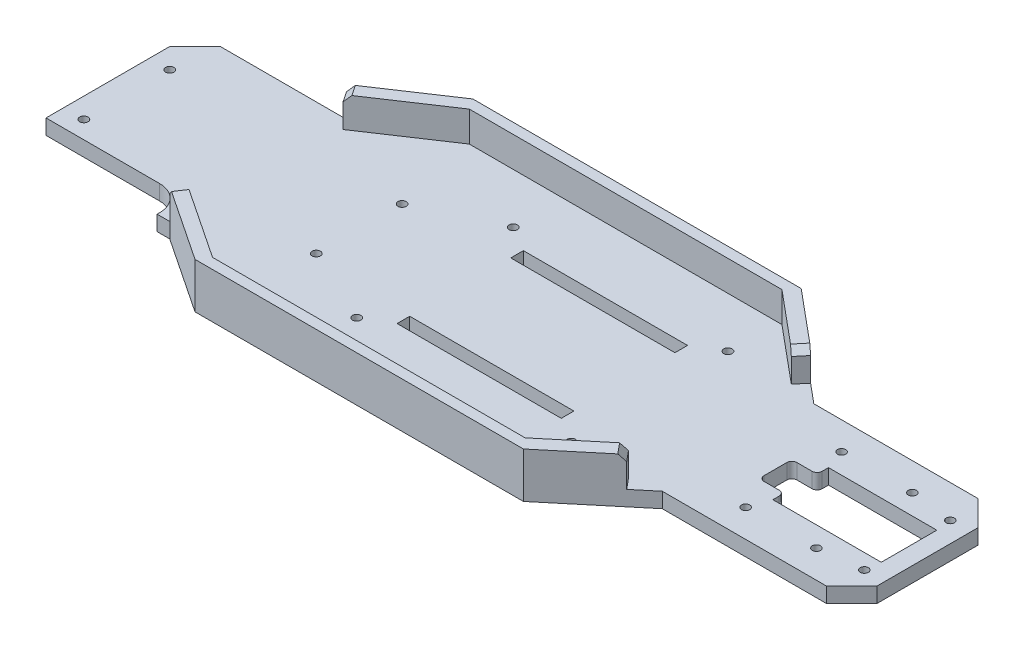
SolidWorks part; units mm, degrees
material "PETG - Polymaker"
ref_plane "Front Plane" through (0, 0, 0) normal (0, 0, 1) x (1, 0, 0)
ref_plane "Top Plane" through (0, 0, 0) normal (0, 1, 0) x (1, 0, 0)
ref_plane "Right Plane" through (0, 0, 0) normal (1, 0, 0) x (0, 0, -1)
sketch "Sketch1" plane through (0, 0, 0) normal (0, 1, 0) x (1, 0, 0)
  line L0 (-235.1499, 0) -> (235.1499, 0) construction
  line L1 (0, 0) -> (0, 52596.8311) construction
  line L2 (-95, 35) -> (-65, 55)
  line L3 (-65, 55) -> (65, 55)
  line L4 (-95, 35) -> (-155, 35)
  line L5 (-155, 35) -> (-155, -35)
  line L6 (-65, -55) -> (65, -55)
  line L7 (-95, -35) -> (-65, -55)
  line L8 (-95, -35) -> (-155, -35)
  line L9 (65, 55) -> (95, 30)
  line L10 (95, 30) -> (170, 30)
  line L11 (170, 30) -> (170, -30)
  line L12 (95, -30) -> (170, -30)
  line L13 (65, -55) -> (95, -30)
  point P3 (0, 0)
  point P10 (-80, 45)
  point P15 (-80, -45)
  point P18 (-155, 0)
  point P19 (0, -55)
  point P20 (0, 55)
  point P23 (170, 0)
  dimension "D1" = 55
  dimension "D2" = 70
  dimension "D3" = 30
  dimension "D4" = 60
  dimension "D5" = 130
  dimension "D6" = 75
  dimension "D7" = 60
  dimension "D8" = 30
  dimension "D9" = 110
extrude "Boss-Extrude1" add sketch "Sketch1" along normal blind 6
sketch "Sketch3" plane through (0, 6, 0) normal (0, 1, 0) x (1, 0, 0)
  line L0 (0, 0) -> (50000, 0) construction
  line L1 (0, 0) -> (0, 50000) construction
  line L2 (0, 55) -> (-65, 55)
  line L3 (65, 55) -> (-65, 55) construction
  line L4 (-65, 55) -> (-95, 35)
  line L5 (-95, 35) -> (-92.2265, 30.8397)
  line L6 (-92.2265, 30.8397) -> (-62.2265, 50.8397)
  line L7 (-62.2265, 50.8397) -> (0, 50.8397)
  line L8 (-65, 55) -> (-62.2265, 50.8397) construction
  line L9 (0, 55) -> (65, 55)
  line L10 (65, 55) -> (87.3178, 36.4018)
  line L11 (87.3178, 36.4018) -> (83.8509, 32.2416)
  line L12 (83.8509, 32.2416) -> (61.5331, 50.8397)
  line L13 (61.5331, 50.8397) -> (0, 50.8397)
  line L14 (61.5331, 50.8397) -> (65, 55) construction
  line L15 (61.5331, -50.8397) -> (65, -55) construction
  line L16 (-65, -55) -> (-62.2265, -50.8397) construction
  line L27 (-65, 55) -> (-95, 35) construction
  line L28 (95, 30) -> (65, 55) construction
  line L29 (61.5331, -50.8397) -> (0, -50.8397)
  line L30 (83.8509, -32.2416) -> (61.5331, -50.8397)
  line L31 (87.3178, -36.4018) -> (83.8509, -32.2416)
  line L32 (65, -55) -> (87.3178, -36.4018)
  line L33 (0, -55) -> (65, -55)
  line L34 (-62.2265, -50.8397) -> (0, -50.8397)
  line L35 (-92.2265, -30.8397) -> (-62.2265, -50.8397)
  line L36 (-95, -35) -> (-92.2265, -30.8397)
  line L37 (-65, -55) -> (-95, -35)
  line L38 (0, -55) -> (-65, -55)
  dimension "D1" = 5
  dimension "D2" = 0
  dimension "D3" = 10
extrude "Chassis-Walls1" add sketch "Sketch3" along normal blind 12
chamfer "Chamfer1" distance 10 angle 45 2 edges at (-155, 3, -35) (-155, 3, 35)
chamfer "Chamfer2" distance 10 angle 45 2 edges at (170, 3, -30) (170, 3, 30)
chamfer "Chamfer3" distance 2.5 angle 45 4 edges at (-93.6132, 18, -32.9199) (85.5843, 18, -34.3217) (-93.6132, 18, 32.9199) (85.5843, 18, 34.3217)
sketch "Sketch4" plane through (0, 0, 0) normal (0, -1, 0) x (1, 0, 0)
  line L0 (0, 0) -> (50000, 0) construction
  line L1 (-147, 17) -> (-55, 17) construction
  line L2 (-155, -25) -> (-155, 25) construction
  circle A0 centre (-147, 17) radius 1.65
  circle A1 centre (-55, 17) radius 1.65
  circle A2 centre (-55, -17) radius 1.65
  circle A3 centre (-147, -17) radius 1.65
  circle A4 centre (-25, 31) radius 1.65
  circle A5 centre (60, 31) radius 1.65
  circle A6 centre (60, -31) radius 1.65
  circle A7 centre (-25, -31) radius 1.65
  dimension "D1" = 3.3
  dimension "D2" = 3.3
  dimension "D6" = 3.3
  dimension "D8" = 3.3
  dimension "D3" = 8
  dimension "D4" = 92
  dimension "D5" = 34
  dimension "D7" = 30
  dimension "D9" = 85
  dimension "D10" = 62
extrude "Cut-Extrude1" cut sketch "Sketch4" against normal blind 10
sketch "Sketch5" plane through (0, 6, 0) normal (0, 1, 0) x (1, 0, 0)
  line L0 (-155, -24) -> (-100, -24)
  line L1 (-155, 25) -> (-155, -25) construction
  line L2 (-100, -24) -> (-100, -35)
  line L3 (-145, -35) -> (-95, -35) construction
  line L4 (-100, -35) -> (-155, -35)
  line L5 (-155, -35) -> (-155, -24)
  dimension "D1" = 55
  dimension "D2" = 11
extrude "Cut-Extrude2" cut sketch "Sketch5" against normal blind 10
sketch "Sketch6" plane through (0, 6, 0) normal (0, 1, 0) x (1, 0, 0)
  line L0 (0, 0) -> (50000, 0) construction
  line L1 (60, 31) -> (-25, 31) construction
  line L2 (17.5, 30.75) -> (17.5, 50030.75) construction
  line L3 (-15, -20) -> (50, -25) construction
  line L4 (-15, 25) -> (50, 25)
  line L5 (-15, 25) -> (-15, 20)
  line L6 (-15, 20) -> (50, 20)
  line L7 (50, 25) -> (50, 20)
  line L8 (-15, 25) -> (50, 20) construction
  line L9 (-15, 20) -> (50, 25) construction
  line L10 (-15, -25) -> (50, -20) construction
  line L11 (50, -25) -> (50, -20)
  line L12 (-15, -20) -> (50, -20)
  line L13 (-15, -25) -> (-15, -20)
  line L14 (-15, -25) -> (50, -25)
  point P9 (17.5, 31)
  point P10 (17.5, 22.5)
  point P19 (17.5, -22.5)
  dimension "D1" = 5
  dimension "D2" = 65
  dimension "D3" = 20
extrude "Cut-Extrude3" cut sketch "Sketch6" against normal through all
fillet "Fillet1" radius 10 1 edges at (-100, 3, 24)
sketch "Sketch7" plane through (0, 6, 0) normal (0, 1, 0) x (1, 0, 0)
  line L0 (175, 0) -> (50175, 0) construction
  line L1 (170, -20) -> (170, 20) construction
  line L3 (120.8, 10) -> (161.7, 10) construction
  line L4 (120.8, 10) -> (120.8, -10) construction
  line L5 (120.8, -10) -> (161.7, -10) construction
  line L6 (161.7, 10) -> (161.7, -10) construction
  line L7 (120.8, 10) -> (161.7, -10) construction
  line L8 (120.8, -10) -> (161.7, 10) construction
  line L9 (119.8, 11) -> (162.7, 11)
  line L10 (119.8, 11) -> (119.8, -11)
  line L11 (119.8, -11) -> (162.7, -11)
  line L12 (162.7, 11) -> (162.7, -11)
  line L13 (119.8, 11) -> (162.7, -11) construction
  line L14 (119.8, -11) -> (162.7, 11) construction
  point P4 (170, 0)
  point P5 (141.25, 0)
  point P10 (141.25, 0)
  dimension "D1" = 20
  dimension "D2" = 40.9
  dimension "D3" = 1
  dimension "D4" = 1
  dimension "D5" = 8.3
extrude "Cut-Extrude4" cut sketch "Sketch7" against normal through all
sketch "Sketch9" plane through (0, 6, 0) normal (0, 1, 0) x (1, 0, 0)
  circle A0 centre (117, -19) radius 1.625
  circle A1 centre (145, -19) radius 1.625
  circle A2 centre (162, -17) radius 1.625
  dimension "D1" = 3.25
  dimension "D2" = 3.25
  dimension "D3" = 3.25
extrude "Cut-Extrude5" cut sketch "Sketch9" against normal through all
mirror "Mirror1" about plane through (0, 0, 0) normal (0, 0, 1) of "Cut-Extrude5"
sketch "Sketch10" plane through (0, 6, 0) normal (0, 1, 0) x (1, 0, 0)
  line L0 (124.8, 0) -> (50124.8, 0) construction
  line L1 (119.8, 11) -> (119.8, -11) construction
  line L2 (119.8, 6.5) -> (109.8, 6.5)
  line L3 (109.8, 6.5) -> (109.8, -6.5)
  line L4 (119.8, 6.5) -> (119.8, -6.5)
  line L5 (119.8, -6.5) -> (109.8, -6.5)
  point P4 (119.8, 0)
  point P10 (119.8, 0)
  point P11 (109.8, 0)
  dimension "D1" = 13
  dimension "D2" = 10
extrude "Servo-Cable-Cutout" cut sketch "Sketch10" against normal blind 10
fillet "Fillet2" radius 2 4 edges at (119.8, 3, -6.5) (119.8, 3, 6.5) (109.8, 3, 6.5) (109.8, 3, -6.5)
equation "\"D6@Sketch4\"=\"D2@Sketch4\""
equation "\"D8@Sketch4\"=\"D2@Sketch4\""
equation "\"D2@Sketch4\"=\"D1@Sketch4\""
equation "\"D2@Sketch9\"=\"D1@Sketch9\""
equation "\"D3@Sketch9\"=\"D1@Sketch9\""
